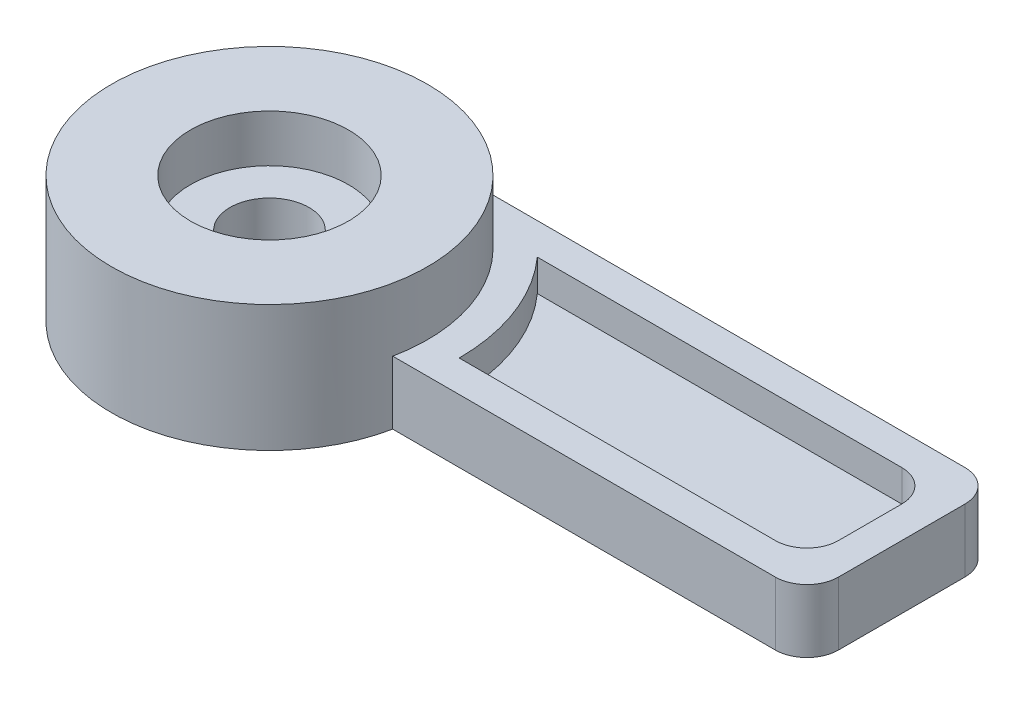
SolidWorks part; units mm, degrees
ref_plane "정면" through (0, 0, 0) normal (0, 0, 1) x (1, 0, 0)
ref_plane "윗면" through (0, 0, 0) normal (0, 1, 0) x (1, 0, 0)
ref_plane "우측면" through (0, 0, 0) normal (1, 0, 0) x (0, 0, -1)
sketch "스케치2" plane through (0, 0, 0) normal (0, 1, 0) x (1, 0, 0)
  line L0 (0, 50) -> (180, 50)
  line L1 (180, 50) -> (180, -10)
  line L2 (180, -10) -> (48.9898, -10)
  line L3 (44.7214, 40) -> (170, 40)
  line L4 (170, 40) -> (170, 0)
  line L5 (170, 0) -> (60, 0)
  line L6 (0, 40) -> (170, 40) construction
  line L8 (170, 0) -> (48.9898, 0) construction
  circle A0 centre (0, 0) radius 50
  arc A1 (60, 0) -> (44.7214, 40) centre (0, 0) ccw
  circle A2 centre (0, 0) radius 60 construction
  dimension "D1" = 100
  dimension "D2" = 180
  dimension "D3" = 60
  dimension "D4" = 10
extrude "보스-돌출1" add sketch "스케치2" along normal blind 20 contours A0 L2 L1 L0 L5 A1 L3 L4 region at (90, 0, -48.1026)
extrude "보스-돌출2" add sketch "스케치2<4>" along normal blind 40 contours A0 region at (0, 0, 0)
sketch "스케치2<4>" plane through (0, 0, 0) normal (0, 1, 0) x (1, 0, 0) same geometry as "스케치2"
extrude "보스-돌출3" add sketch "스케치2<5>" along normal blind 10 contours L3 L4 L5 A1
sketch "스케치2<5>" plane through (0, 0, 0) normal (0, 1, 0) x (1, 0, 0) same geometry as "스케치2"
fillet "필렛1" radius 10 4 edges at (180, 10, -50) (170, 15, -40) (170, 15, 0) (180, 10, 10)
hole_wizard "M1.6 남비 머리 나사용 카운터보어1" positions "스케치4" profile "스케치3" counterbore size "M1.6" standard "ISO" end condition through all
sketch "스케치4" plane through (0, 40, 0) normal (0, 1, 0) x (1, 0, 0)
  point P0 (0, 0)
sketch "스케치3" plane through (0, 40, 0) normal (1, 0, 0) x (0, 0, 1)
  line L0 (0, 0) -> (0, 40)
  line L1 (0, 40) -> (12.5, 40)
  line L3 (12.5, 40) -> (12.5, 15)
  line L4 (12.5, 15) -> (25, 15)
  line L5 (25, 15) -> (25, 0)
  line L7 (25, 0) -> (0, 0)
  line L11 (0, -6.35) -> (0, 107.95) construction
  dimension "관통 구멍 지름" = 25
  dimension "관통 구멍 깊이" = 40
  dimension "카운터보어 지름" = 50
  dimension "카운터보어 깊이" = 15
